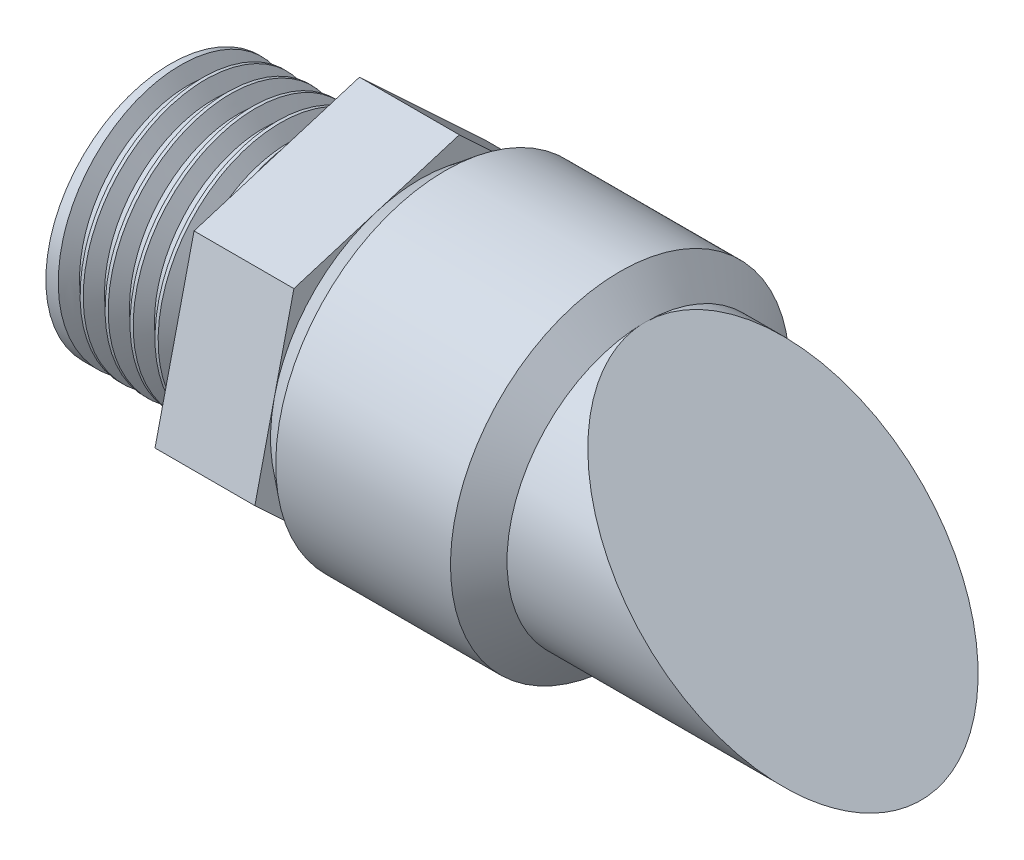
SolidWorks part; units mm, degrees
ref_plane "Спереди" through (0, 0, 0) normal (0, 0, 1) x (1, 0, 0)
ref_plane "Сверху" through (0, 0, 0) normal (0, 1, 0) x (1, 0, 0)
ref_plane "Справа" through (0, 0, 0) normal (1, 0, 0) x (0, 0, -1)
sketch "Эскиз1" plane through (0, 0, 0) normal (0, 0, 1) x (1, 0, 0)
  line L0 (-6.4481, 4.8954) -> (-0.4478, 4.8954)
  line L1 (-0.4478, 4.8954) -> (-0.4478, 5.8954)
  line L2 (-0.4478, 5.8954) -> (3.5522, 5.8954)
  line L3 (3.5522, 5.8954) -> (4.5522, 6.6866)
  line L4 (4.5522, 6.6866) -> (11.5522, 6.6866)
  line L5 (11.5522, 6.6866) -> (12.5522, 5.4228)
  line L6 (12.5522, 5.4228) -> (24.5522, 5.4228)
  line L7 (24.5522, 5.4228) -> (24.5522, -0.1046)
  line L8 (24.5522, -0.1046) -> (-6.4481, -0.1046)
  line L9 (-6.4481, -0.1046) -> (-6.4481, 4.8954)
  dimension "D1" = 6.0003
  dimension "D2" = 5
  dimension "D3" = 6
  dimension "D4" = 4
  dimension "D5" = 1
  dimension "D6" = 7
  dimension "D7" = 1
  dimension "D8" = 12
  dimension "D9" = 6.7912
  dimension "D10" = 5.5274
revolve "Повернуть1" add sketch "Эскиз1" angle 360 about L8 other way angle 360
sketch "Эскиз2" plane through (-0.4478, 0, 0) normal (-1, 0, 0) x (0, 0, 1)
  line L1 (-1.5633, 6.6449) -> (-6.6269, 1.9163)
  line L2 (-6.6269, 1.9163) -> (-5.0636, -4.8332)
  line L3 (-5.0636, -4.8332) -> (1.5633, -6.8541)
  line L4 (1.5633, -6.8541) -> (6.6269, -2.1255)
  line L5 (6.6269, -2.1255) -> (5.0636, 4.624)
  line L6 (5.0636, 4.624) -> (-1.5633, 6.6449)
  circle A0 centre (0, -0.1046) radius 6 construction
extrude "Бобышка-Вытянуть1" add sketch "Эскиз2" against normal blind 4
thread "Резьба1" pitch 1 method cut profile "Профиль резьбы1" start angle 0, offset 0, length 0, pitch 1, diameter 10
ref_plane "Плоскость1" through (-6.4481, -0.1046, -5) normal (0, -1, 0) x (0, 0, -1)
sketch "Профиль резьбы1" plane through (-6.4481, -0.1046, -5) normal (0, -1, 0) x (0, 0, -1)
  line L0 (0, 0) -> (0, 1) construction
  line L11 (0, 0) -> (0, 0.875)
  line L12 (0, 0.875) -> (-0.5413, 0.5625)
  line L13 (-0.5413, 0.5625) -> (-0.5413, 0.3125)
  line L15 (-0.5413, 0.3125) -> (0, 0)
  line L17 (-0.5413, 0.4375) -> (0, 0.4375) construction
  point P2 (0, 0)
  dimension "Pitch" = 1
  dimension "Profile_Angle" = 60
  dimension "Profile_Land" = 0.25
  dimension "Profile_Height" = 0.5413
sketch "Эскиз7" plane through (0, 0, 0) normal (0, 0, 1) x (1, 0, 0)
  line L0 (12.5522, 5.4228) -> (24.0874, -6.1124)
  line L1 (24.0874, -6.1124) -> (25.373, -6.1124)
  line L2 (25.373, -6.1124) -> (25.373, -3.1229)
  line L3 (25.373, -3.1229) -> (25.373, 7.5419)
  line L4 (25.373, 7.5419) -> (12.5522, 7.5419)
  line L5 (12.5522, 7.5419) -> (12.5522, 5.4228)
extrude "Вырез-Вытянуть2" cut sketch "Эскиз7" against normal through all both and the other way through all
sketch "Эскиз8" plane through (-6.4481, 0, 0) normal (-1, 0, 0) x (0, 0, 1)
  circle A0 centre (0, -0.1046) radius 3
extrude "Вырез-Вытянуть3" cut sketch "Эскиз8" against normal blind 6
